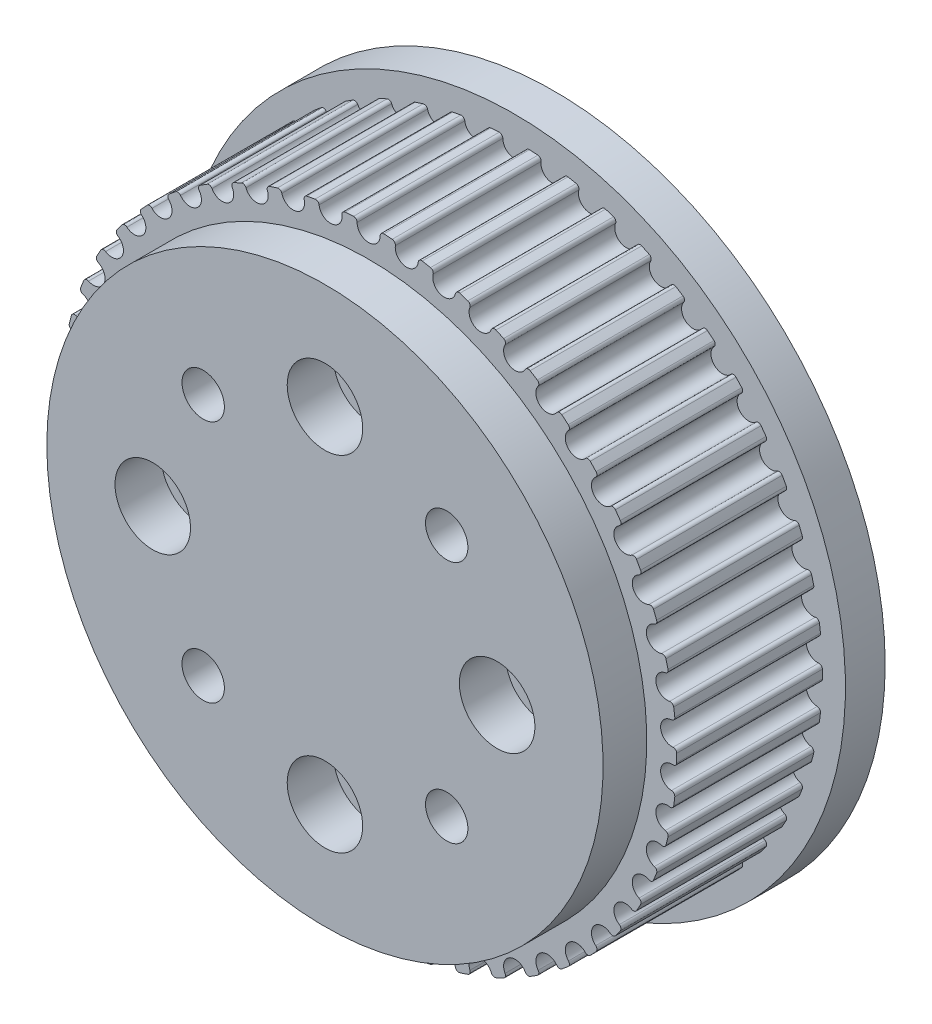
SolidWorks part; units mm, degrees
ref_plane "Front Plane" through (0, 0, 0) normal (1, 0, 0) x (0, 1, 0)
ref_plane "Top Plane" through (0, 0, 0) normal (0, 0, 1) x (0, 1, 0)
ref_plane "Right Plane" through (0, 0, 0) normal (0, 1, 0) x (-1, 0, 0)
sketch "Sketch1" plane through (0, 0, 0) normal (0, 0, 1) x (0, 1, 0)
  line L0 (0, 0) -> (0, 23.2582)
  line L1 (0, 0) -> (1.3869, 22.0447) construction
  line L2 (1.3869, 22.0447) -> (1.4416, 22.9129) construction
  line L3 (2.915, 23.0748) -> (0, 0)
  arc A1 (0.6393, 23.2495) -> (2.2797, 23.1462) centre (1.4416, 22.9129) ccw
  arc A2 (0, 23.2582) -> (0.6393, 23.2495) centre (0, 0) cw
  arc A3 (2.915, 23.0748) -> (2.2797, 23.1462) centre (0, 0) ccw
  dimension "D1" = 3.6
  dimension "D2" = 23.2582
extrude "Boss-Extrude1" add sketch "Sketch1" along normal blind 11 from offset 3
fillet "Fillet1" radius 0.26 2 edges at (-23.2495, 0.6393, 8.5) (-23.1462, 2.2797, 8.5)
pattern_circular "CirPattern1" count 50 over 360 about axis through (0, 0, 14) along (0, 0, -1) of "Fillet1", "Boss-Extrude1"
sketch "Sketch2" plane through (0, 0, 0) normal (0, 0, 1) x (0, 1, 0)
  circle A0 centre (0, 0) radius 25
  circle A1 centre (0, 0) radius 21
  dimension "D1" = 50
  dimension "D2" = 42
extrude "Boss-Extrude2" add sketch "Sketch2" along normal up to surface (3 mm away) contours A1 | A0 A1 region at (0, -24.2929, 0) region at (0, 0, 0) up to face at (0, 0, 3)
extrude "Boss-Extrude3" add sketch "Sketch2<3>" along normal blind 3.3 from surface contours A1 region at (0, 0, 0) starting at face at (0, 0, 14)
sketch "Sketch2<3>" plane through (0, 0, 0) normal (0, 0, 1) x (0, 1, 0) same geometry as "Sketch2"
sketch "Sketch3" plane through (0, 0, 17.3) normal (0, 0, 1) x (1, 0, 0)
  circle A0 centre (0, 0) radius 13 construction
  circle A1 centre (0, 13) radius 1.6
  circle A2 centre (0, 13) radius 2.85
  circle A3 centre (13, 0) radius 2.85
  circle A4 centre (13, 0) radius 1.6
  circle A5 centre (0, -13) radius 2.85
  circle A6 centre (0, -13) radius 1.6
  circle A7 centre (-13, 0) radius 2.85
  circle A8 centre (-13, 0) radius 1.6
  point P18 (0, 0)
  dimension "D1" = 26
  dimension "D2" = 3.2
  dimension "D3" = 5.7
  dimension "D4" = 4
extrude "Cut-Extrude1" cut sketch "Sketch3" against normal through all both and the other way through all contours A8 | A1 | A4 | A6 region at (0, 13, 17.3) region at (13, 0, 17.3) region at (0, -13, 17.3) region at (-13, 0, 17.3)
extrude "Cut-Extrude2" cut sketch "Sketch3<3>" against normal blind 3.5 and the other way through all
sketch "Sketch3<3>" plane through (0, 0, 17.3) normal (0, 0, 1) x (1, 0, 0) same geometry as "Sketch3"
sketch "Sketch4" plane through (0, 0, 0) normal (0, 0, -1) x (1, 0, 0)
  line L0 (0, 0) -> (9.1924, 9.1924) construction
  line L1 (11.9424, -11.9424) -> (6.4424, -11.9424)
  line L2 (6.4424, 11.9424) -> (11.9424, 11.9424)
  line L3 (6.4424, 11.9424) -> (6.4424, 6.4424)
  line L4 (6.4424, 6.4424) -> (11.9424, 6.4424)
  line L5 (11.9424, 11.9424) -> (11.9424, 6.4424)
  line L6 (6.4424, 11.9424) -> (11.9424, 6.4424) construction
  line L7 (6.4424, 6.4424) -> (11.9424, 11.9424) construction
  line L8 (6.4424, -6.4424) -> (6.4424, -11.9424)
  line L9 (11.9424, -6.4424) -> (6.4424, -6.4424)
  line L10 (11.9424, -6.4424) -> (11.9424, -11.9424)
  line L11 (-11.9424, -11.9424) -> (-11.9424, -6.4424)
  line L12 (-6.4424, -6.4424) -> (-11.9424, -6.4424)
  line L13 (-6.4424, -11.9424) -> (-6.4424, -6.4424)
  line L14 (-6.4424, -11.9424) -> (-11.9424, -11.9424)
  line L15 (-11.9424, 11.9424) -> (-6.4424, 11.9424)
  line L16 (-6.4424, 6.4424) -> (-6.4424, 11.9424)
  line L17 (-11.9424, 6.4424) -> (-6.4424, 6.4424)
  line L18 (-11.9424, 6.4424) -> (-11.9424, 11.9424)
  circle A0 centre (0, 0) radius 13 construction
  circle A1 centre (9.1924, 9.1924) radius 1.6
  circle A2 centre (9.1924, -9.1924) radius 1.6
  circle A3 centre (-9.1924, -9.1924) radius 1.6
  circle A4 centre (-9.1924, 9.1924) radius 1.6
  point P31 (0, 0)
  dimension "D2" = 3.2
  dimension "D1" = 5.5
  dimension "D3" = 4
extrude "Cut-Extrude3" cut sketch "Sketch4" against normal through all contours A4 | A1 | A2 | A3 region at (9.1924, -9.1924, 0) region at (9.1924, 9.1924, 0) region at (-9.1924, 9.1924, 0) region at (-9.1924, -9.1924, 0)
extrude "Cut-Extrude4" cut sketch "Sketch4<3>" against normal blind 3
sketch "Sketch4<3>" plane through (0, 0, 0) normal (0, 0, -1) x (1, 0, 0) same geometry as "Sketch4"
equation "\"D2@Sketch1\"=(50*3) / (PI * 2) - 0.615"
